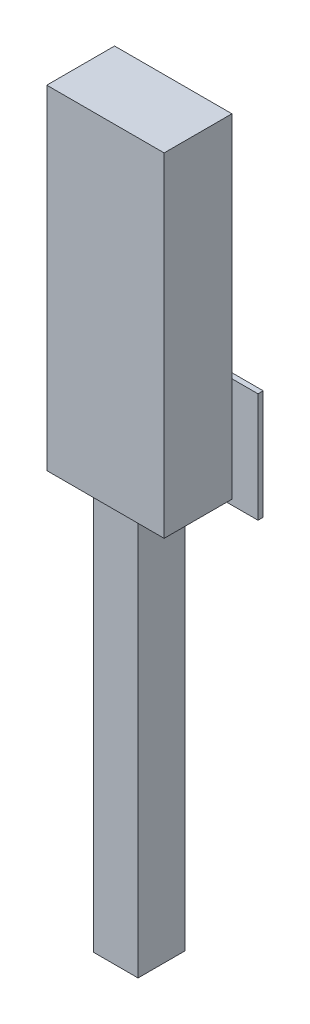
SolidWorks part; units mm, degrees
ref_plane "Front Plane" through (0, 0, 0) normal (0, 0, 1) x (1, 0, 0)
ref_plane "Top Plane" through (0, 0, 0) normal (0, 1, 0) x (1, 0, 0)
ref_plane "Right Plane" through (0, 0, 0) normal (1, 0, 0) x (0, 0, -1)
other "Configuration Table"
sketch "Sketch1" plane through (0, 0, 0) normal (1, 0, 0) x (0, 0, -1)
  line L1 (-51, 155) -> (-77, 155)
  line L2 (-51, 155) -> (-51, 283)
  line L3 (-51, 283) -> (-77, 283)
  line L4 (-77, 155) -> (-77, 283)
  line L5 (-51, 155) -> (-77, 283) construction
  line L6 (-51, 283) -> (-77, 155) construction
extrude "reflector" add sketch "Sketch1" along normal blind 45 from offset 44 separate body
sketch "Sketch2" plane through (0, 0, 0) normal (1, 0, 0) x (0, 0, -1)
  line L1 (-45, 158) -> (-74, 158)
  line L2 (-45, 158) -> (-45, 280)
  line L3 (-45, 280) -> (-74, 280)
  line L4 (-74, 158) -> (-74, 280)
  line L5 (-45, 158) -> (-74, 280) construction
  line L6 (-45, 280) -> (-74, 158) construction
extrude "cavity" add sketch "Sketch2" along normal blind 39 from offset 47 separate body
combine bodies "Combine1" operation type subtract main body 102 bodies to subtract 103
sketch "Sketch3" plane through (0, 0, 0) normal (0, 1, 0) x (1, 0, 0)
  circle A0 centre (66.34, -59.5) radius 5
extrude "r7s_lamp" add sketch "Sketch3" along normal blind 118 from offset 160 separate body
sketch "Sketch4" plane through (0, 0, 0) normal (1, 0, 0) x (0, 0, -1)
  line L0 (-77, 155) -> (-51, 155) construction
  line L1 (-55, 0) -> (-73, 0)
  line L2 (-55, 0) -> (-55, 155)
  line L3 (-55, 155) -> (-73, 155)
  line L4 (-73, 0) -> (-73, 155)
  line L5 (-55, 0) -> (-73, 155) construction
  line L6 (-55, 155) -> (-73, 0) construction
  point P0 (-64, 77.5)
extrude "heater_column" add sketch "Sketch4" along normal blind 17 from offset 58 separate body
sketch "Sketch5" plane through (0, 0, 0) normal (1, 0, 0) x (0, 0, -1)
  line L1 (-46, 150) -> (-48, 150)
  line L2 (-46, 150) -> (-46, 192)
  line L3 (-46, 192) -> (-48, 192)
  line L4 (-48, 150) -> (-48, 192)
  line L5 (-46, 150) -> (-48, 192) construction
  line L6 (-46, 192) -> (-48, 150) construction
extrude "heat_shield" add sketch "Sketch5" along normal blind 66 from offset 30 separate body
